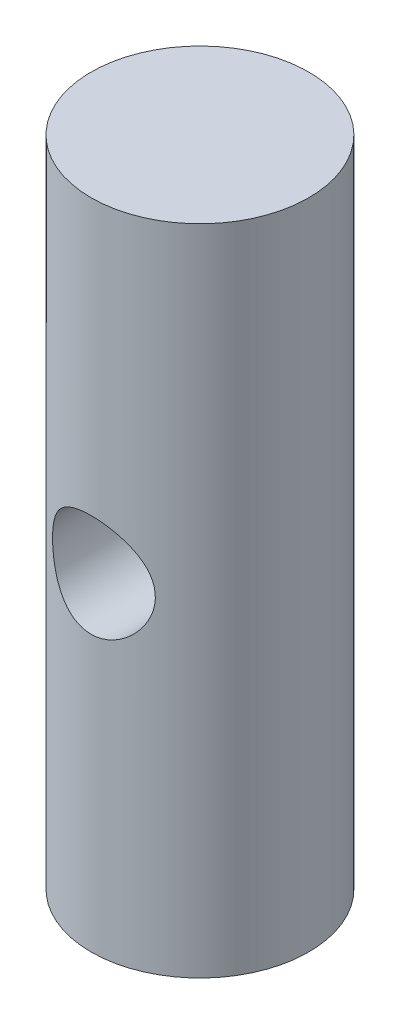
SolidWorks part; units mm, degrees
ref_plane "Front Plane" through (0, 0, 0) normal (0, 0, 1) x (1, 0, 0)
ref_plane "Top Plane" through (0, 0, 0) normal (0, 1, 0) x (1, 0, 0)
ref_plane "Right Plane" through (0, 0, 0) normal (1, 0, 0) x (0, 0, -1)
sketch "Sketch1" plane through (0, 0, 0) normal (0, 1, 0) x (1, 0, 0)
  circle A0 centre (0, 0) radius 3.175
  dimension "D1" = 6.35
extrude "Boss-Extrude1" add sketch "Sketch1" along normal blind 19.05 contours A0
sketch "Sketch2" plane through (0, 0, 0) normal (0, 0, 1) x (1, 0, 0)
  line L0 (-3.175, 9.525) -> (3.175, 9.525) construction
  line L1 (-3.175, 19.05) -> (-3.175, 0) construction
  line L2 (3.175, 0) -> (3.175, 19.05) construction
  circle A0 centre (0, 9.525) radius 1.4986
  dimension "D1" = 2.9972
extrude "Cut-Extrude1" cut sketch "Sketch2" against normal up to surface and the other way blind 19.05 up to face at (0, 19.05, 3.175)
sketch "Sketch3" plane through (0, 0, 0) normal (0, -1, 0) x (1, 0, 0)
  circle A0 centre (0, 0) radius 2.286
  dimension "D1" = 4.572
ref_plane "Plane1" through (0, 9.525, 0) normal (0, -1, 0) x (-1, 0, 0)
